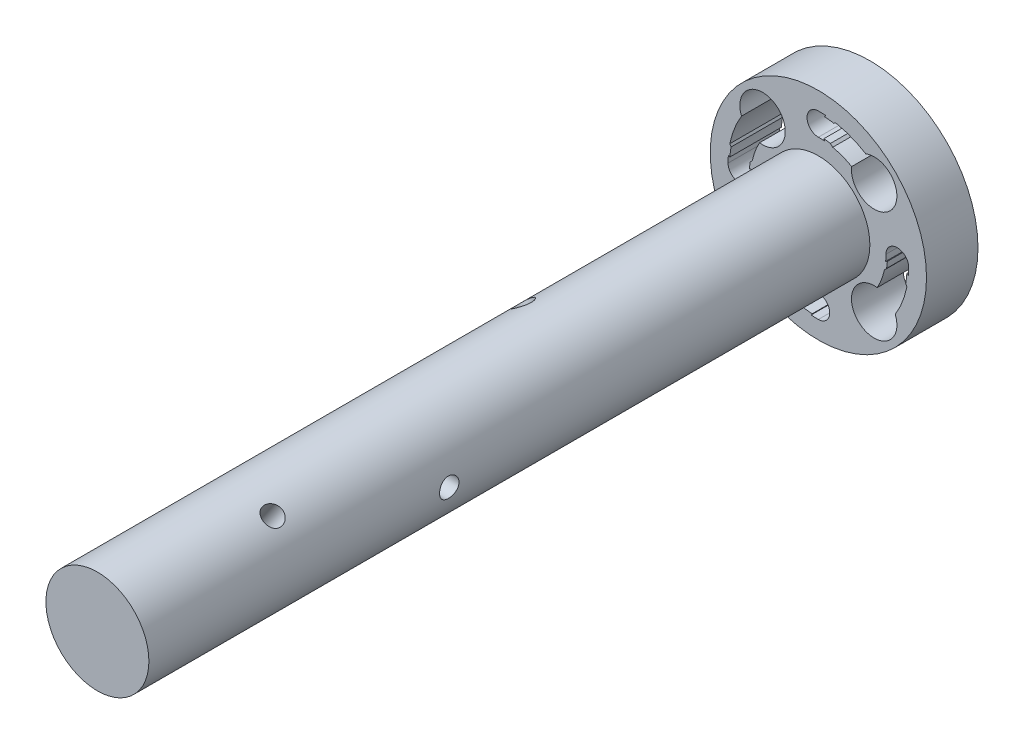
SolidWorks part; units mm, degrees
ref_plane "Front Plane" through (0, 0, 0) normal (0, 0, 1) x (1, 0, 0)
ref_plane "Top Plane" through (0, 0, 0) normal (0, 1, 0) x (1, 0, 0)
ref_plane "Right Plane" through (0, 0, 0) normal (1, 0, 0) x (0, 0, -1)
sketch "Sketch1" plane through (0, 0, 0) normal (0, 0, 1) x (1, 0, 0)
  circle A0 centre (0, 0) radius 4.7625
  circle A1 centre (0, 0) radius 10
  circle A2 centre (0, 0) radius 3.175
  circle A5 centre (0, 0) radius 3.175
  circle A7 centre (0, 0) radius 3.175
  circle A9 centre (0, 0) radius 3.175
  point P19 (0, 0)
  dimension "D1" = 9.525
  dimension "D2" = 20
  dimension "D3" = 6.35
  dimension "D6" = 4
extrude "Boss-Extrude1" add sketch "Sketch1" along normal blind 66.675 contours A0
extrude "Boss-Extrude2" add sketch "Sketch1<4>" against normal blind 4.7625 contours A1 A0 | A0 A2 region at (-4.6278, 0, 0) region at (-9.7172, 0, 0)
sketch "Sketch1<4>" plane through (0, 0, 0) normal (0, 0, 1) x (1, 0, 0) same geometry as "Sketch1"
fillet "Fillet1" radius 3.175 1 edges at (3.175, 0, 0)
sketch "Sketch2" plane through (0, 0, 0) normal (0, 1, 0) x (1, 0, 0)
  line L0 (-4.7625, -66.675) -> (4.7625, -66.675) construction
  line L1 (0, -66.675) -> (0, -53.1812) construction
  line L2 (0, -53.1812) -> (0, -38.8937) construction
  line L3 (0, -38.8937) -> (0, -24.6062) construction
  dimension "D2" = 13.4937
  dimension "D1" = 14.2875
  dimension "D3" = 14.2875
sketch "Sketch3" plane through (0, 0, 0) normal (1, 0, 0) x (0, 0, -1)
  circle A0 centre (-38.8937, 0) radius 0.9
  dimension "D1" = 1.8
extrude "Cut-Extrude2" cut sketch "Sketch3" against normal through all both and the other way through all
ref_plane "Plane1" through (0, 0, 0) normal (0.5736, 0.8192, 0) x (0, 0, -1)
ref_plane "Plane2" through (0, 0, 0) normal (-0.5736, 0.8192, 0) x (0, 0, -1)
sketch "Sketch4" plane through (0, 0, 0) normal (0.5736, 0.8192, 0) x (0, 0, -1)
  circle A0 centre (-53.1812, 0) radius 0.9
  dimension "D1" = 1.8
extrude "Cut-Extrude3" cut sketch "Sketch4" against normal through all both and the other way through all
sketch "Sketch5" plane through (0, 0, 0) normal (-0.5736, 0.8192, 0) x (0, 0, -1)
  circle A0 centre (-24.6062, 0) radius 0.9
  dimension "D1" = 1.8
extrude "Cut-Extrude4" cut sketch "Sketch5" against normal through all both and the other way through all
sketch "Sketch6" plane through (0, 0, -4.7625) normal (0, 0, -1) x (-1, 0, 0)
  line L0 (0, 7.3) -> (0, 0) construction
  line L1 (0, 0) -> (-5.1619, 5.1619) construction
  arc A0 (0, 6.25) -> (0, 8.35) centre (0, 7.3) ccw
  arc A4 (-4.3782, 7.1102) -> (-3.0802, 5.4383) centre (-5.1619, 5.1619) ccw
  arc A5 (0, 6.25) -> (-3.0802, 5.4383) centre (0, 0) ccw
  arc A6 (0, 8.35) -> (-4.3782, 7.1102) centre (0, 0) ccw
  point P12 (0, 0)
  dimension "D3" = 2.1
  dimension "D5" = 4.2
  dimension "D1" = 7.3
  dimension "D4" = 45
extrude "Cut-Extrude5" cut sketch "Sketch6" against normal through all
sketch "Sketch7" plane through (0, 0, -4.7625) normal (0, 0, -1) x (-1, 0, 0)
  line L0 (0, 0) -> (-2.5511, 14.4681)
  line L1 (0, 7.3) -> (0, 0) construction
  line L2 (-0.987, 8.8162) -> (0, 7.3)
  line L3 (0, 7.3) -> (-0.6791, 6.0653)
  line L4 (-3.0442, 8.9578) -> (0, 7.3)
  line L5 (0, 7.3) -> (-2.1902, 5.3347)
  arc A0 (0, 8.35) -> (-0.5729, 8.18) centre (0, 7.3) ccw
  arc A1 (0, 6.25) -> (-3.0802, 5.4383) centre (0, 0) ccw construction
  arc A4 (0, 8.2) -> (-4.2995, 6.9824) centre (0, 0) ccw
  arc A5 (-0.5729, 8.18) -> (-1.4239, 8.0754) centre (0, 0) ccw
  arc A6 (0, 8.35) -> (-4.3782, 7.1102) centre (0, 0) ccw construction
  arc A7 (0, 6.4) -> (-3.1541, 5.5688) centre (0, 0) ccw
  arc A8 (-0.506, 6.38) -> (-1.1113, 6.3028) centre (0, 0) ccw
  arc A9 (0, 6.25) -> (-1.3296, 6.1069) centre (0, 0) ccw
  arc A10 (-0.506, 6.38) -> (0, 6.25) centre (0, 7.3) ccw
  arc A11 (0, 8.35) -> (-1.6323, 8.1889) centre (0, 0) ccw
  arc M8 (0, 6.25) -> (-3.0802, 5.4383) centre (0, 0) ccw
  arc M10 (-4.3782, 7.1102) -> (0, 8.35) centre (0, 0) cw
  dimension "D3" = 10
  dimension "D2" = 0.15
extrude "Boss-Extrude3" add sketch "Sketch7" against normal up to surface (4.7625 mm away) contours A10 A8 L0 M8 | A5 A0 L0 M10 | L0 L5 M8 | L4 L0 M10 region at (0.8239, 6.2716, -4.7625) region at (1.1751, 6.1889, -4.7625) region at (1.5022, 8.1627, -4.7625) region at (1.0287, 8.2063, -4.7625) up to face at (2.4096, 6.3129, 0)
pattern_circular "CirPattern1" count 4 over 360 about axis through (0, 0, -4.7625) along (0, 0, 1) of "Cut-Extrude5", "Boss-Extrude3"
equation "\"normtol\" = 0.01in"
equation "\"loosetol\" = 0.02in"
equation "\"tighttol\" = 0.005in"
equation "\"Fry height\"= 0.5in"
equation "\"Fry spacing\"= 0.5625in"
equation "\"Potato width\"= \"Fry spacing\" * 4"
equation "\"Potato length\"= 80mm"
equation "\"top robot surface separation\" = 0.6875"
equation "\"D2@Sketch2\"=1/4+\"Fry spacing\"/2"
equation "\"D1@Sketch3\"=1.8mm"
equation "\"D1@Sketch2\"=\"Fry spacing\""
equation "\"D3@Sketch2\"=\"Fry spacing\""
equation "\"D1@Sketch4\"=1.8mm"
equation "\"D1@Sketch5\"=1.8mm"
equation "\"D1@Sketch6\"=7.3mm"
equation "\"D3@Sketch6\"=2.1mm"
equation "\"D5@Sketch6\"=4.2mm"
equation "\"D2@Sketch1\"=20mm"
equation "\"D1@Sketch7\"=0.15mm"
equation "\"D2@Sketch7\"=0.15mm"
